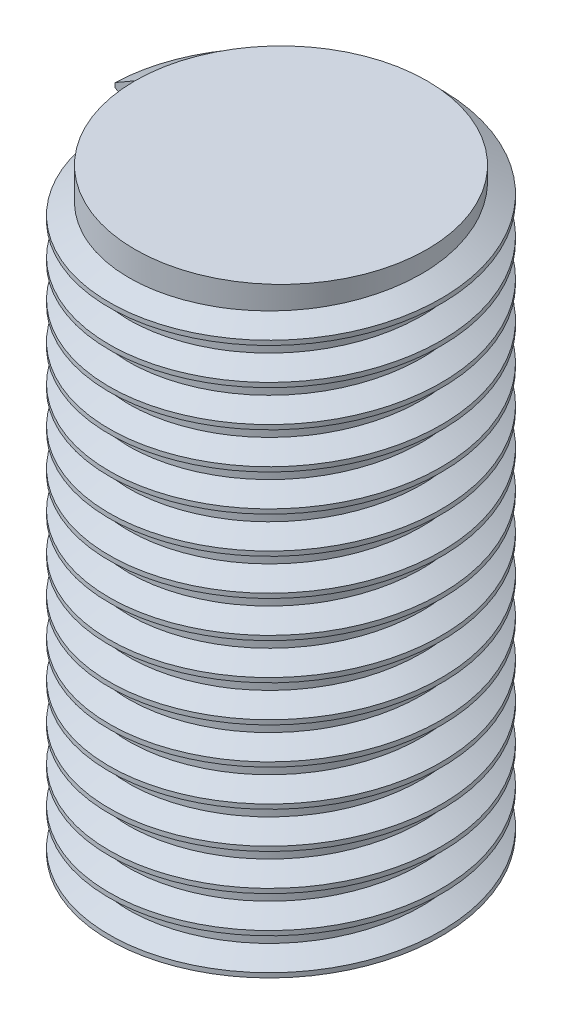
SolidWorks part; units mm, degrees
ref_plane "Front Plane" through (0, 0, 0) normal (0, 0, 1) x (1, 0, 0)
ref_plane "Top Plane" through (0, 0, 0) normal (0, 1, 0) x (1, 0, 0)
ref_plane "Right Plane" through (0, 0, 0) normal (1, 0, 0) x (0, 0, -1)
sketch "Sketch1" plane through (0, 0, 0) normal (0, 1, 0) x (1, 0, 0)
  circle A0 centre (0, 0) radius 1
  dimension "D1" = 2
extrude "Boss-Extrude1" add sketch "Sketch1" along normal blind 4
sketch "Sketch2" plane through (0, 0, 0) normal (1, 0, 0) x (0, 0, -1)
  line L0 (-1, 0) -> (1, 0) construction
  circle A0 centre (0, 40) radius 0.5
  dimension "D1" = 1
  dimension "D2" = 40
thread "Thread1" pitch 0.25 method extrude profile "Thread Profile1" start angle 0, offset 0, length 4, pitch 0.25, diameter 2
ref_plane "Plane1" through (-1, 4, 0) normal (0, 0, 1) x (-1, 0, 0)
sketch "Thread Profile1" plane through (-1, 4, 0) normal (0, 0, 1) x (-1, 0, 0)
  line L0 (0, 0) -> (0, 0.25) construction
  line L1 (0, 0) -> (0.1353, 0.0781)
  line L2 (0.1353, 0.0781) -> (0.1353, 0.1094)
  line L3 (0.1353, 0.1094) -> (0, 0.1875)
  line L4 (0.1353, 0.0937) -> (0, 0.0937) construction
  line L11 (0, 0) -> (0, 0.1875)
  point P2 (0, 0)
  dimension "Pitch" = 0.25
  dimension "Profile_Angle" = 60
  dimension "Profile_Land" = 0.0312
  dimension "Profile_Height" = 0.1353
